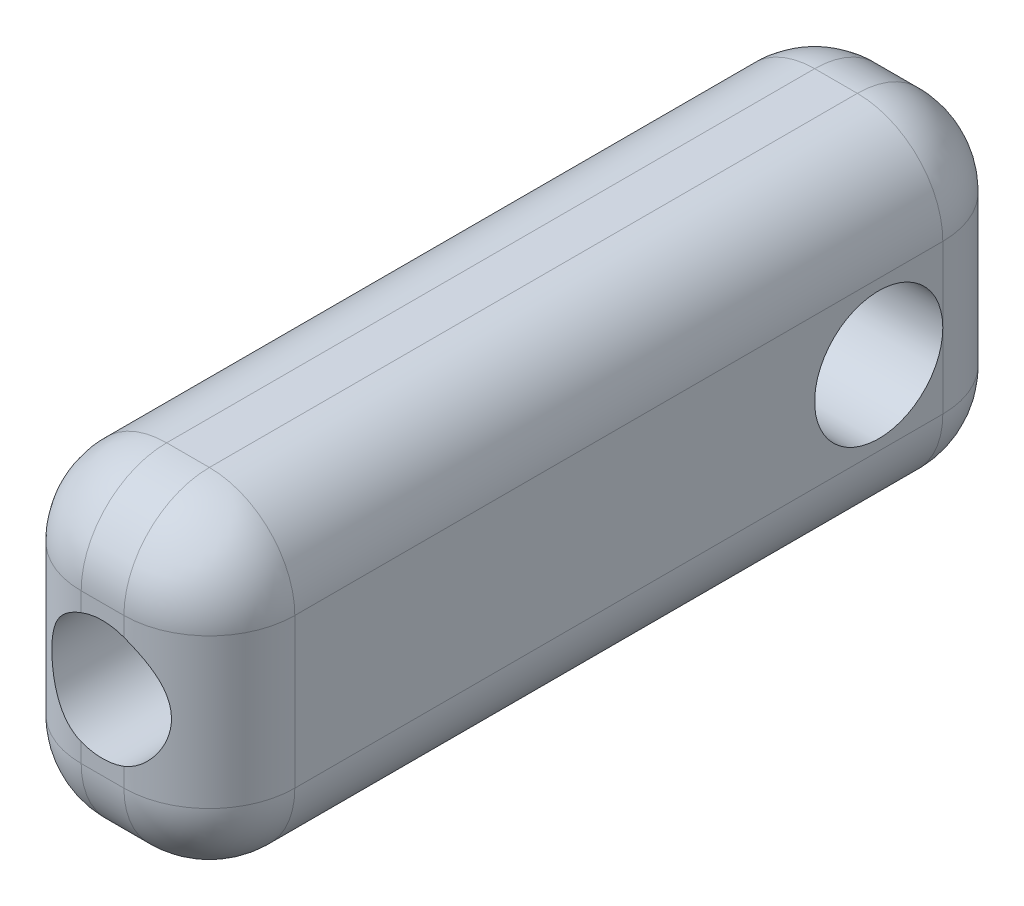
SolidWorks part; units mm, degrees
ref_plane "Front Plane" through (0, 0, 0) normal (0, 0, 1) x (1, 0, 0)
ref_plane "Top Plane" through (0, 0, 0) normal (0, 1, 0) x (1, 0, 0)
ref_plane "Right Plane" through (0, 0, 0) normal (1, 0, 0) x (0, 0, -1)
sketch "Sketch1" plane through (0, 0, 0) normal (0, 1, 0) x (1, 0, 0)
  line L0 (0, 0) -> (0, 24.3398)
  line L3 (0, 24.3398) -> (6.35, 24.3398)
  line L4 (6.35, 24.3398) -> (6.35, 0)
  line L6 (6.35, 0) -> (0, 0)
  dimension "D1" = 6.35
extrude "Boss-Extrude1" add sketch "Sketch1" along normal mid plane 9.525
sketch "Sketch2" plane through (0, 0, 0) normal (0, 0, 1) x (1, 0, 0)
  line L0 (6.35, 0) -> (3.175, 0) construction
  line L2 (3.175, 0) -> (0, 0) construction
  line L3 (6.35, 4.7625) -> (6.35, -4.7625) construction
  circle A0 centre (3.175, 0) radius 1.778
  dimension "D1" = 3.556
extrude "Cut-Extrude1" cut sketch "Sketch2" against normal blind 9.525
sketch "Sketch3" plane through (0, 0, 0) normal (-1, 0, 0) x (0, 0, 1)
  line L0 (-19.8948, 0) -> (-19.8948, 4.7625) construction
  line L2 (-19.8948, 0) -> (-19.8948, -4.7625) construction
  line L4 (-24.3398, -4.7625) -> (0, -4.7625) construction
  line L6 (-24.3398, 4.7625) -> (0, 4.7625) construction
  line L8 (-24.3398, 4.7625) -> (-24.3398, -4.7625) construction
  circle A0 centre (-19.8948, 0) radius 1.905
  dimension "D1" = 3.81
  dimension "D2" = 4.445
extrude "Cut-Extrude2" cut sketch "Sketch3" against normal blind 9.525
fillet "Fillet1" radius 2.54 12 edges at (6.35, -4.7625, -12.1699) (0, -4.7625, -12.1699) (3.175, -4.7625, 0) (0, 4.7625, -12.1699) (6.35, 4.7625, -12.1699) (3.175, 4.7625, 0) (6.35, 0, -24.3398) (3.175, 4.7625, -24.3398) (0, 0, -24.3398) (3.175, -4.7625, -24.3398) (0, 0, 0) (6.35, 0, 0)
